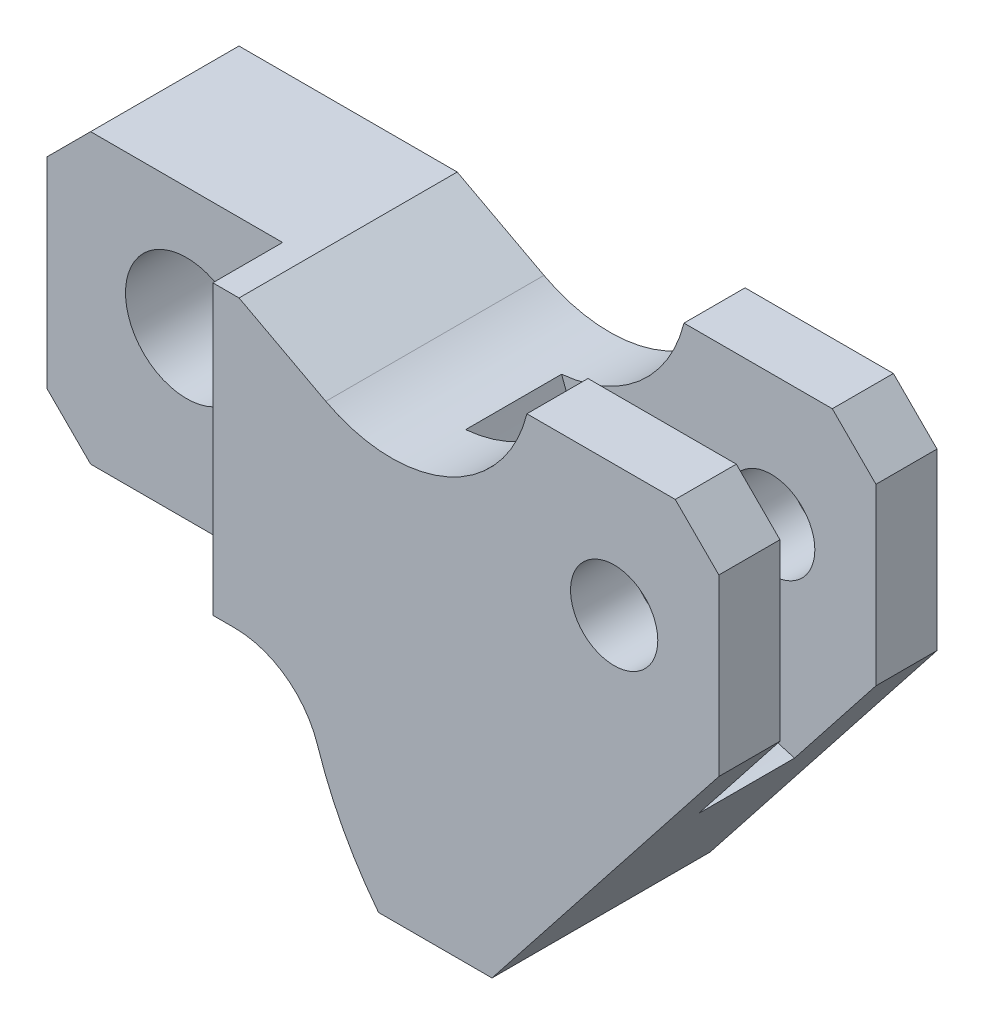
SolidWorks part; units mm, degrees
ref_plane "Front Plane" through (0, 0, 0) normal (0, 0, 1) x (1, 0, 0)
ref_plane "Top Plane" through (0, 0, 0) normal (0, 1, 0) x (1, 0, 0)
ref_plane "Right Plane" through (0, 0, 0) normal (1, 0, 0) x (0, 0, -1)
sketch "Sketch1" plane through (0, 0, 0) normal (0, 0, 1) x (1, 0, 0)
  line L0 (25.5324, -3.84) -> (15.5324, -3.84)
  line L2 (37.5324, -3.84) -> (37.5324, -28.84)
  line L3 (37.5324, -28.84) -> (11.5324, -61.84)
  line L4 (11.5324, -61.84) -> (-1.4676, -61.84)
  line L5 (-17.9657, -41.84) -> (-47.4676, -41.84)
  line L7 (-47.4676, -41.84) -> (-47.4676, -8.84)
  line L9 (-47.4676, -8.84) -> (-17.4552, -8.84)
  line L10 (0, 0) -> (31.5474, 0) construction
  line L11 (25.5324, -3.84) -> (25.5324, -18.84) construction
  line L12 (25.5324, -3.84) -> (37.5324, -3.84)
  line L13 (-20.4676, -8.84) -> (-20.4676, -41.84)
  line L14 (-17.4552, -8.84) -> (-7.5115, -14.1272)
  line L15 (-17.4552, -8.84) -> (-3.9802, -8.84) construction
  line L16 (-47.4676, -8.84) -> (-20.4676, -8.84) construction
  line L17 (-47.4676, -8.84) -> (-47.4676, -7.4026) construction
  arc A0 (-7.5115, -14.1272) -> (15.5324, -3.84) centre (0, 0) ccw
  arc A2 (-8.4621, -48.7286) -> (-17.9657, -41.84) centre (-17.9657, -51.84) ccw
  circle A3 centre (25.5324, -18.84) radius 5
  arc A4 (-1.4676, -61.84) -> (-8.4621, -48.7286) centre (32.4036, -35.3496) cw
  circle A5 centre (-31.4676, -22.84) radius 7
  point P1 (20.5324, -3.84)
  point P3 (0, 0)
  point P22 (0, 0)
  point P26 (0, 0)
  point P27 (0, 0)
  point P30 (0, 0)
  point P31 (-6.2683, -49.6398)
  point P32 (0, 0)
  dimension "D1" = 16
  dimension "D4" = 10
  dimension "D10" = 10
  dimension "D11" = 43
  dimension "D17" = 14
  dimension "D2" = 22
  dimension "D3" = 3.84
  dimension "D5" = 12
  dimension "D6" = 15
  dimension "D7" = 25
  dimension "D8" = 26
  dimension "D9" = 13
  dimension "D12" = 20
  dimension "D13" = 33
  dimension "D14" = 14
  dimension "D15" = 16
  dimension "D16" = 85
  dimension "D18" = 27
  dimension "D19" = 28
  dimension "D20" = 58
extrude "Boss-Extrude1" add sketch "Sketch1" along normal mid plane 25 contours L13 L9 L7 L5 A5 | A4 L4 L3 L2 L12 L0 A0 L14 L9 L13 L5 A2 A3 region at (8.1151, -30.9474, 0) region at (-20.894, -25.34, 0)
extrude "Cut-Extrude1" cut sketch "Sketch1<3>" against normal blind 8 from offset 12.5 contours L13 L9 L7 L5 A5 region at (-20.894, -25.34, 0)
sketch "Sketch1<3>" plane through (0, 0, 0) normal (0, 0, 1) x (1, 0, 0) same geometry as "Sketch1"
chamfer "Chamfer1" distance 5 angle 45 3 edges at (37.5324, -3.84, 0) (-47.4676, -41.84, -4) (-47.4676, -8.84, -4)
sketch "Sketch4" plane through (0, 0, 0) normal (0, 0, 1) x (1, 0, 0)
  line L0 (37.5324, -8.84) -> (37.5324, -28.84) construction
  line L1 (15.5324, -3.84) -> (32.5324, -3.84) construction
  line L2 (37.5324, -8.84) -> (37.5324, -28.84)
  line L3 (15.5324, -3.84) -> (32.5324, -3.84)
  line L4 (32.5324, -3.84) -> (37.5324, -3.84) construction
  line L5 (37.5324, -3.84) -> (37.5324, -8.84) construction
  line L6 (37.5324, -28.84) -> (11.5324, -61.84) construction
  line L7 (37.5324, -28.84) -> (28.2057, -40.6777)
  line L8 (32.5324, -3.84) -> (37.5324, -8.84)
  arc A0 (1.5066, -15.9289) -> (28.2057, -40.6777) centre (37.5324, -3.84) ccw
  arc A1 (-7.5115, -14.1272) -> (15.5324, -3.84) centre (0, 0) ccw construction
  arc A2 (1.5066, -15.9289) -> (15.5324, -3.84) centre (0, 0) ccw
  dimension "D1" = 38
extrude "Cut-Extrude2" cut sketch "Sketch4" against normal mid plane 11
